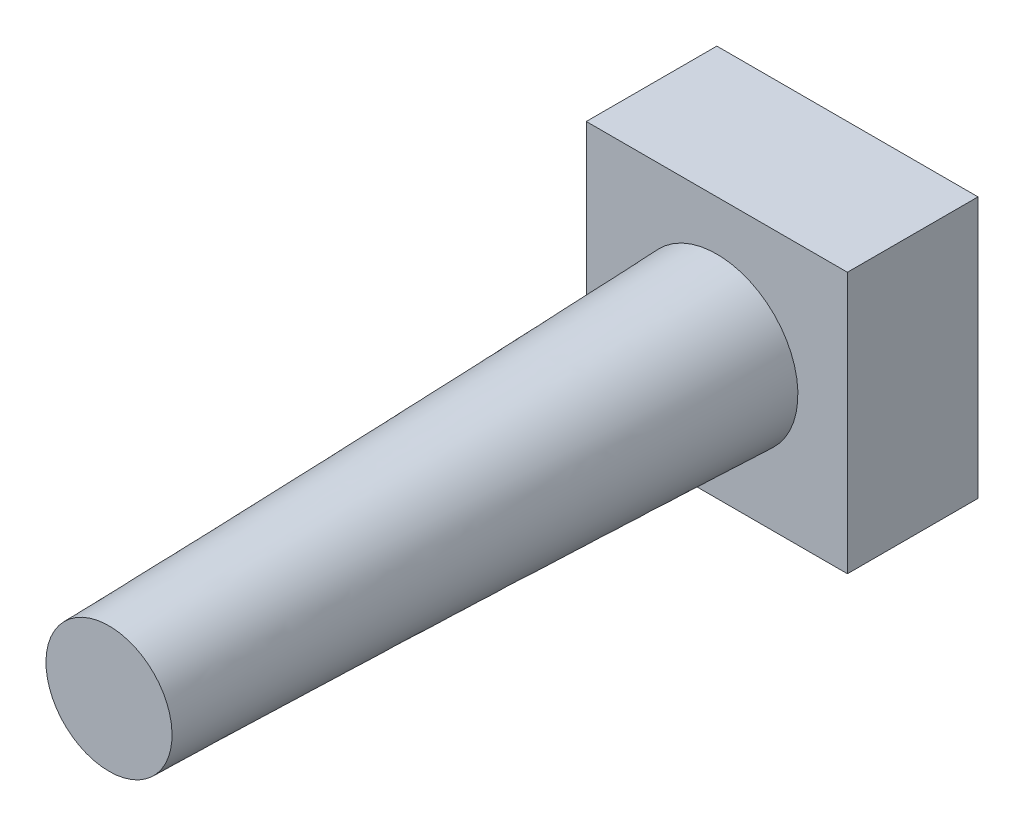
SolidWorks part; units mm, degrees
ref_plane "Спереди" through (0, 0, 0) normal (0, 0, 1) x (1, 0, 0)
ref_plane "Сверху" through (0, 0, 0) normal (0, 1, 0) x (1, 0, 0)
ref_plane "Справа" through (0, 0, 0) normal (1, 0, 0) x (0, 0, -1)
sketch "Sketch1" plane through (0, 0, 0) normal (0, 0, 1) x (1, 0, 0)
  line L1 (2.9, -2.9) -> (-2.9, -2.9)
  line L2 (2.9, -2.9) -> (2.9, 2.9)
  line L3 (2.9, 2.9) -> (-2.9, 2.9)
  line L4 (-2.9, -2.9) -> (-2.9, 2.9)
  line L5 (2.9, -2.9) -> (-2.9, 2.9) construction
  line L6 (2.9, 2.9) -> (-2.9, -2.9) construction
  point P0 (0, 0)
  dimension "D1" = 5.8
extrude "Boss-Extrude1" add sketch "Sketch1" along normal blind 2.9
sketch "Sketch2" plane through (0, 0, 2.9) normal (0, 0, 1) x (1, 0, 0)
  circle A0 centre (0, 0) radius 1.8
  dimension "D1" = 3.6
ref_plane "Plane1" through (0, 0, 16.4) normal (0, 0, 1) x (1, 0, 0)
sketch "Sketch3" plane through (0, 0, 16.4) normal (0, 0, 1) x (1, 0, 0)
  circle A0 centre (0, 0) radius 1.4
  dimension "D1" = 2.8
loft "Loft1" add profiles "Sketch3", "Sketch2" connector at (0.8774, 1.091, 16.4) connector at (1.5482, 0.9182, 2.9)
